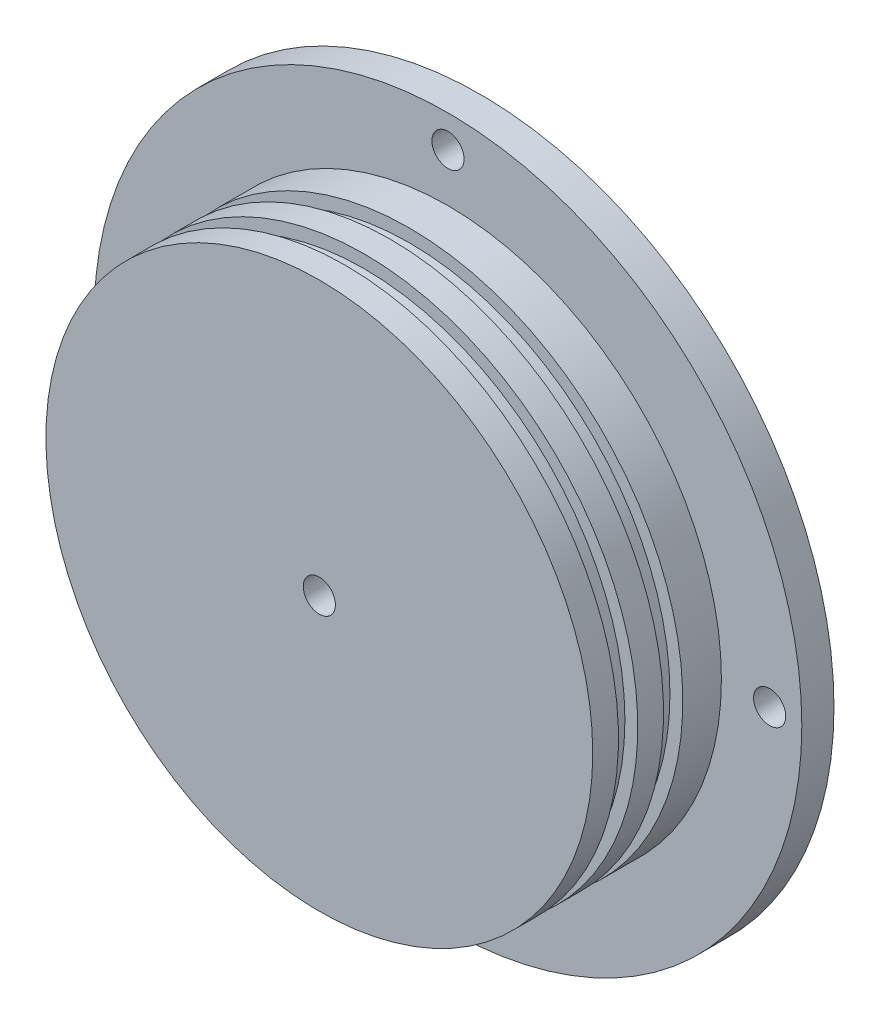
SolidWorks part; units mm, degrees
ref_plane "Front Plane" through (0, 0, 0) normal (0, 0, 1) x (1, 0, 0)
ref_plane "Top Plane" through (0, 0, 0) normal (0, 1, 0) x (1, 0, 0)
ref_plane "Right Plane" through (0, 0, 0) normal (1, 0, 0) x (0, 0, -1)
sketch "Sketch1" plane through (0, 0, 0) normal (0, 0, 1) x (1, 0, 0)
  circle A0 centre (0, 0) radius 55
  dimension "D1" = 110
extrude "Boss-Extrude1" add sketch "Sketch1" along normal blind 5
sketch "Sketch3" plane through (0, 0, 0) normal (0, 0, -1) x (-1, 0, 0)
  circle A0 centre (0, 50) radius 2.5
  point P5 (0, 0)
  dimension "D1" = 50
  dimension "D2" = 5
extrude "Cut-Extrude1" cut sketch "Sketch3" against normal through all
pattern_circular "CirPattern1" count 4 over 360 about axis through (0, 0, 5) along (0, 0, -1) of "Cut-Extrude1" reverse direction yes
sketch "Sketch2" plane through (0, 0, 5) normal (0, 0, 1) x (1, 0, 0)
  circle A0 centre (0, 0) radius 42.5
  dimension "D1" = 85
extrude "Boss-Extrude2" add sketch "Sketch2" along normal blind 20
sketch "Sketch4" plane through (0, 0, 0) normal (1, 0, 0) x (0, 0, -1)
  line L0 (-5, 42.5) -> (-25, 42.5) construction
  line L5 (-14, 42.5) -> (-11, 42.5)
  line L6 (-14, 42.5) -> (-14, 40.5)
  line L7 (-14, 40.5) -> (-11, 40.5)
  line L8 (-11, 42.5) -> (-11, 40.5)
  line L9 (-21, 42.5) -> (-21, 40.5)
  line L10 (-5, 42.5) -> (-5, -42.5) construction
  line L11 (0, 0) -> (-33.7056, 0) construction
  line L12 (-21, 40.5) -> (-18, 40.5)
  line L13 (-18, 42.5) -> (-18, 40.5)
  line L14 (-21, 42.5) -> (-18, 42.5)
  point P8 (-11, 41.5)
  dimension "D1" = 3
  dimension "D2" = 6
  dimension "D3" = 2
  dimension "D4" = 4
revolve "Cut-Revolve1" cut sketch "Sketch4" angle 360 about L11
sketch "Sketch5" plane through (0, 0, 0) normal (0, 0, -1) x (-1, 0, 0)
  circle A0 centre (0, 0) radius 2.5
  dimension "D1" = 5
extrude "Cut-Extrude2" cut sketch "Sketch5" against normal through all
sketch "Sketch6" plane through (0, 0, 0) normal (0, 0, -1) x (-1, 0, 0)
  circle A0 centre (0, 0) radius 20
  dimension "D1" = 40
extrude "Cut-Extrude3" cut sketch "Sketch6" against normal blind 10
